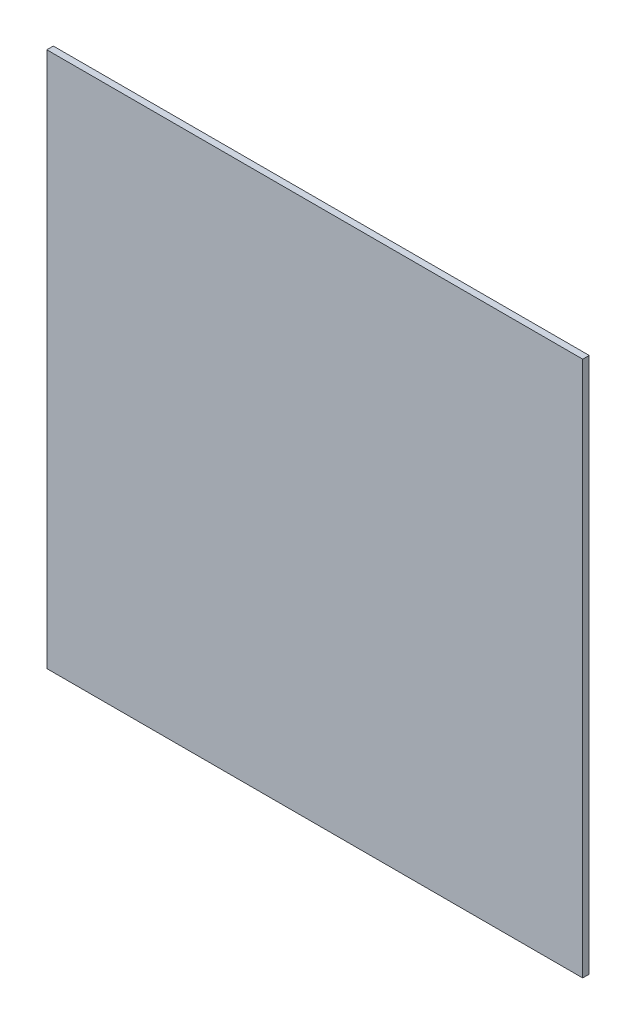
SolidWorks part; units mm, degrees
material "5052-O"
ref_plane "Front Plane" through (0, 0, 0) normal (0, 0, 1) x (1, 0, 0)
ref_plane "Top Plane" through (0, 0, 0) normal (0, 1, 0) x (1, 0, 0)
ref_plane "Right Plane" through (0, 0, 0) normal (1, 0, 0) x (0, 0, -1)
sketch "Sketch2" plane through (0, 0, 0) normal (0, 0, 1) x (1, 0, 0)
  line L1 (-165, 165) -> (165, 165)
  line L2 (-165, 165) -> (-165, -165)
  line L3 (-165, -165) -> (165, -165)
  line L4 (165, 165) -> (165, -165)
  dimension "D1" = 330
  dimension "D2" = 330
  dimension "D3" = 165
  dimension "D4" = 165
extrude "Boss-Extrude2" add sketch "Sketch2" along normal blind 4
